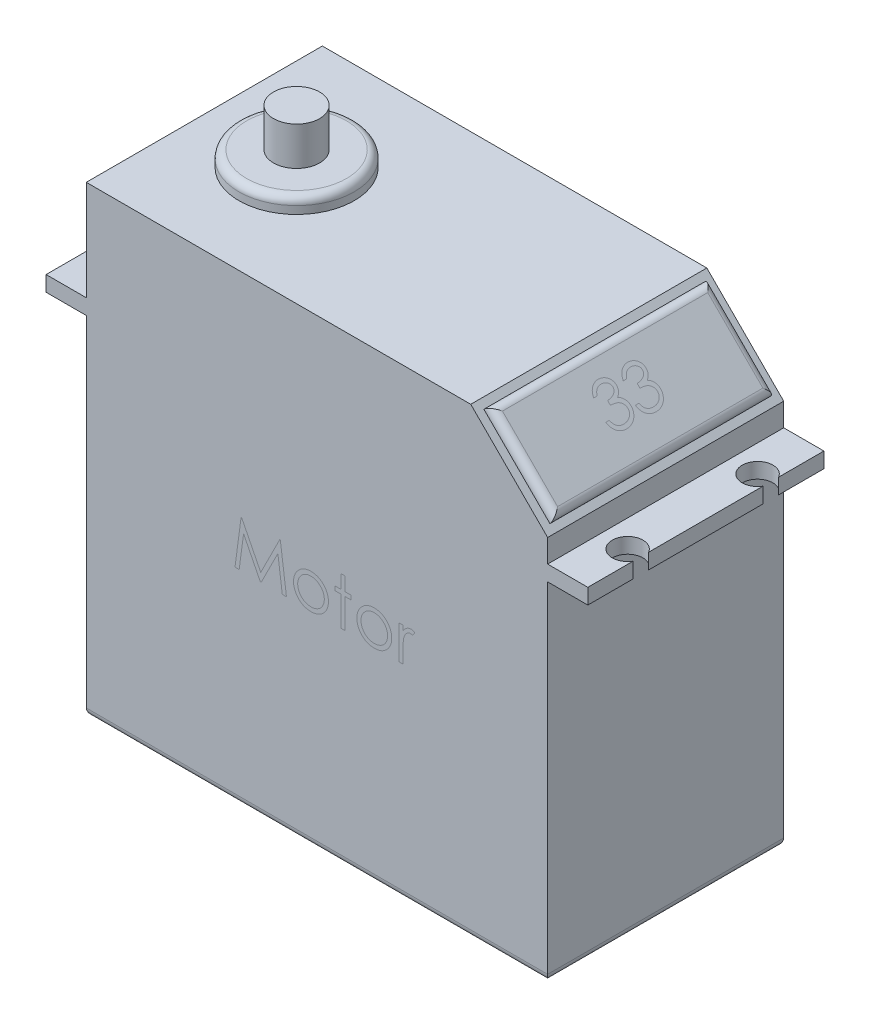
SolidWorks part; units mm, degrees
ref_plane "Front Plane" through (0, 0, 0) normal (0, 0, 1) x (1, 0, 0)
ref_plane "Top Plane" through (0, 0, 0) normal (0, 1, 0) x (1, 0, 0)
ref_plane "Right Plane" through (0, 0, 0) normal (1, 0, 0) x (0, 0, -1)
sketch "Sketch1" plane through (0, 0, 0) normal (0, 0, 1) x (1, 0, 0)
  line L1 (-30, 30.1) -> (30, 30.1)
  line L2 (-30, 30.1) -> (-30, -30.1)
  line L3 (-30, -30.1) -> (30, -30.1)
  line L4 (30, 30.1) -> (30, -30.1)
  line L5 (-30, 30.1) -> (30, -30.1) construction
  line L6 (-30, -30.1) -> (30, 30.1) construction
  point P0 (0, 0)
  dimension "D1" = 60
  dimension "D2" = 60.2
extrude "Boss-Extrude1" add sketch "Sketch1" along normal blind 30.7
sketch "Sketch2" plane through (0, 30.1, 0) normal (0, 1, 0) x (1, 0, 0)
  line L0 (0, 31.4535) -> (0, -44.6708) construction
  line L1 (-55.2372, -15.35) -> (52.8871, -15.35) construction
  line L2 (30, -30.7) -> (30, 0) construction
  line L3 (30, 0) -> (-30, 0) construction
  line L4 (-35.2244, 0) -> (35.2244, 0)
  line L5 (-35.2244, 0) -> (-35.2244, -5.8869)
  line L6 (-35.2244, -30.7) -> (35.2244, -30.7)
  line L7 (35.2244, 0) -> (35.2244, -5.8869)
  line L8 (-35.2244, 0) -> (35.2244, -30.7) construction
  line L9 (-35.2244, -30.7) -> (35.2244, 0) construction
  line L10 (-35.2244, -7.9131) -> (-35.2244, -22.7869)
  line L11 (-35.2244, -24.8131) -> (-35.2244, -30.7)
  line L12 (35.2244, -7.9131) -> (35.2244, -22.7869)
  line L13 (35.2244, -24.8131) -> (35.2244, -30.7)
  arc A0 (35.2244, -5.8869) -> (35.2244, -7.9131) centre (33.5, -6.9) ccw
  arc A1 (35.2244, -24.8131) -> (35.2244, -22.7869) centre (33.5, -23.8) cw
  arc A2 (-35.2244, -24.8131) -> (-35.2244, -22.7869) centre (-33.5, -23.8) ccw
  arc A3 (-35.2244, -5.8869) -> (-35.2244, -7.9131) centre (-33.5, -6.9) cw
  point P7 (30, -15.35)
  point P16 (0, -15.35)
  dimension "D1" = 4
  dimension "D2" = 67
  dimension "D3" = 16.9
extrude "Boss-Extrude2" add sketch "Sketch2" along normal blind 2 from offset 15 offset against normal yes
sketch "Sketch3" plane through (0, 30.1, 0) normal (0, 1, 0) x (1, 0, 0)
  line L0 (-30, -30.7) -> (-30, 0) construction
  circle A0 centre (-18, -15.35) radius 3
  dimension "D1" = 6
  dimension "D2" = 12
extrude "Boss-Extrude3" add sketch "Sketch3" along normal blind 7
chamfer "Chamfer1" distance 10 angle 45 1 edges at (30, 30.1, 15.35)
sketch "Sketch4" plane through (0, 0, 30.7) normal (0, 0, 1) x (1, 0, 0)
  text T0 "Motor" font "Century Gothic" height 6
split line "Split Line1"
sketch "Sketch5" plane through (0, 30.1, 0) normal (0, 1, 0) x (1, 0, 0)
  circle A0 centre (-18, -15.35) radius 3 construction
  circle A1 centre (-18, -15.35) radius 3
  circle A2 centre (-18, -15.35) radius 7.5
  dimension "D1" = 15
extrude "Boss-Extrude4" add sketch "Sketch5" along normal blind 2
fillet "Fillet1" radius 1 1 edges at (-18, 32.1, 22.85)
fillet "Fillet2" radius 1 4 edges at (-30, -30.1, 15.35) (0, -30.1, 30.7) (30, -30.1, 15.35) (0, -30.1, 0)
sketch "Sketch6" plane through (25.05, 25.05, 0) normal (0.7071, 0.7071, 0) x (0, 0, -1)
  line L8 (-29.7, 6.1418) -> (-29.7, -6.0004)
  line L9 (-29.7, -6.0004) -> (-1, -6.0004)
  line L10 (-1, -6.0004) -> (-1, 6.1418)
  line L11 (-1, 6.1418) -> (-29.7, 6.1418)
  line L12 (-29.7, 6.1418) -> (-29.7, -6.0004)
  line L13 (-29.7, -6.0004) -> (-1, -6.0004)
  line L14 (-1, -6.0004) -> (-1, 6.1418)
  line L15 (-1, 6.1418) -> (-29.7, 6.1418)
  dimension "D1" = 1
extrude "Boss-Extrude5" add sketch "Sketch6" along normal blind 1
fillet "Fillet3" radius 1 4 edges at (25.7071, 25.8071, 1) (30, 21.5142, 15.35) (25.7071, 25.8071, 29.7) (21.4142, 30.1, 15.35)
sketch "Sketch7" plane through (25.7571, 25.7571, 0) normal (0.7071, 0.7071, 0) x (0, 0, -1)
  text T0 "33" font "Century Gothic" height 5
split line "Split Line2"
